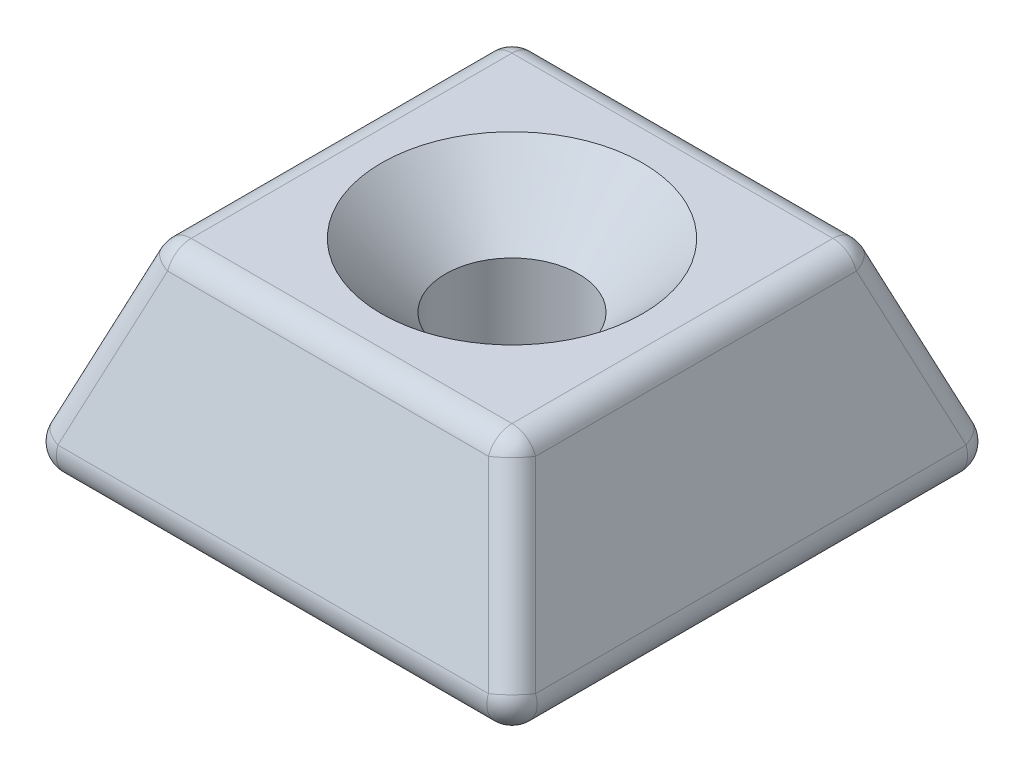
SolidWorks part; units mm, degrees
ref_plane "Front Plane" through (0, 0, 0) normal (0, 0, 1) x (1, 0, 0)
ref_plane "Top Plane" through (0, 0, 0) normal (0, 1, 0) x (1, 0, 0)
ref_plane "Right Plane" through (0, 0, 0) normal (1, 0, 0) x (0, 0, -1)
sketch "Sketch1" plane through (0, 0, 0) normal (0, 1, 0) x (1, 0, 0)
  line L1 (0, 0) -> (20, 0)
  line L2 (0, 0) -> (0, 20)
  line L3 (0, 20) -> (20, 20)
  line L4 (20, 0) -> (20, 20)
  dimension "D1" = 20
  dimension "D2" = 20
extrude "Boss-Extrude1" add sketch "Sketch1" along normal blind 8 draft 20
sketch "Sketch4" plane through (0, 8, 0) normal (0, 1, 0) x (1, 0, 0)
  line L1 (17.0882, 17.0882) -> (2.9118, 17.0882) construction
  line L2 (10, 17.0882) -> (10, 2.9118) construction
  line L3 (2.9118, 2.9118) -> (17.0882, 2.9118) construction
  line L10 (2.9118, 10) -> (17.0882, 10) construction
  line L11 (2.9118, 17.0882) -> (2.9118, 2.9118) construction
  line L12 (17.0882, 2.9118) -> (17.0882, 17.0882) construction
  point P0 (10, 10)
  point P36 (0, 0)
  point P37 (10, 10)
hole_wizard "CSK for M5 Flat Head Machine Screw1" positions "Sketch4" profile "Sketch3" countersink size "M5" standard "ANSI Metric" end condition through all
sketch "Sketch3" plane through (10, 8, -10) normal (1, 0, 0) x (0, 0, 1)
  line L0 (0, 0) -> (0, 8)
  line L1 (0, 8) -> (2.65, 8)
  line L2 (2.65, 8) -> (2.65, 2.55)
  line L3 (2.65, 2.55) -> (5.2, 0)
  line L5 (5.2, 0) -> (0, 0)
  line L6 (-2.65, 2.55) -> (-5.2, 0) construction
  line L11 (0, -6.35) -> (0, 107.95) construction
  dimension "Thru Hole Dia." = 5.3
  dimension "Thru Hole Depth" = 8
  dimension "Near C'Sink Dia." = 10.4
  dimension "Near C'Sink Angle" = 90
fillet "Fillet1" radius 1 12 edges at (10, 8, -17.0882) (17.0882, 8, -10) (20, 0, -10) (18.5441, 4, -18.5441) (10, 0, -20) (10, 8, -2.9118) (18.5441, 4, -1.4559) (10, 0, 0) (1.4559, 4, -18.5441) (2.9118, 8, -10) (1.4559, 4, -1.4559) (0, 0, -10)
